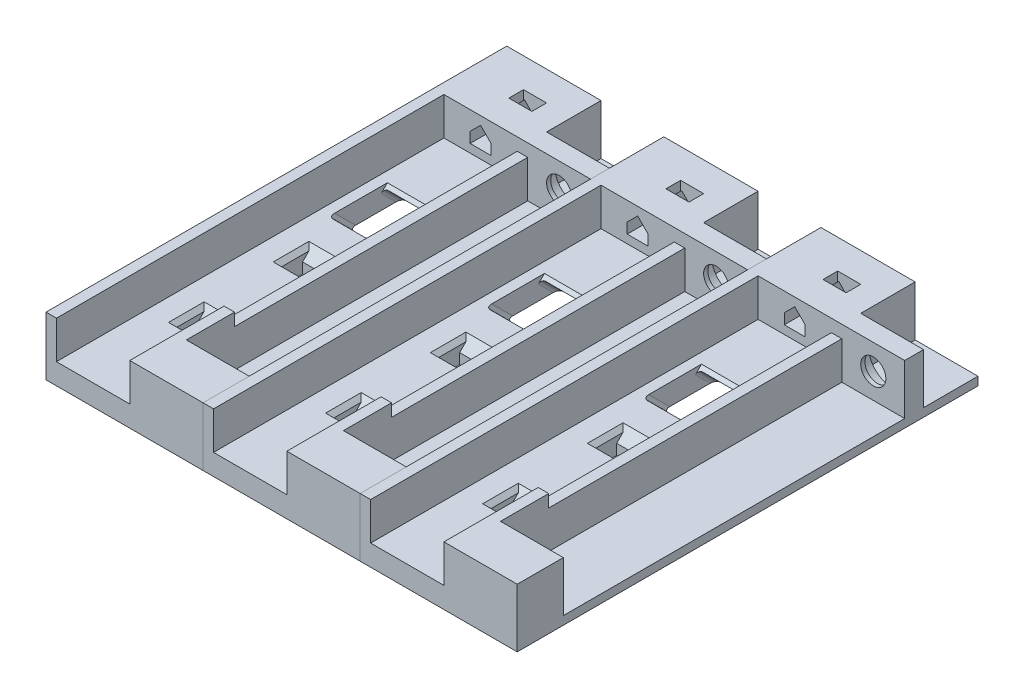
SolidWorks part; units mm, degrees
ref_plane "Płaszczyzna przednia" through (0, 0, 0) normal (0, 0, 1) x (1, 0, 0)
ref_plane "Płaszczyzna górna" through (0, 0, 0) normal (0, 1, 0) x (1, 0, 0)
ref_plane "Płaszczyzna prawa" through (0, 0, 0) normal (1, 0, 0) x (0, 0, -1)
sketch "Szkic1" plane through (0, 0, 0) normal (0, 0, 1) x (1, 0, 0)
  line L0 (0, 0) -> (0, 40.355) construction
  line L2 (17.5, 18) -> (-17.5, 18)
  line L3 (17.5, 18) -> (17.5, 0)
  line L4 (17.5, 0) -> (-17.5, 0)
  line L5 (-17.5, 18) -> (-17.5, 0)
  line L6 (17.5, 18) -> (-17.5, 0) construction
  line L7 (17.5, 0) -> (-17.5, 18) construction
  line L8 (17.5, 18) -> (22.5, 18)
  line L9 (52.5, -6) -> (22.5, -6)
  line L10 (52.5, -6) -> (52.5, 18)
  line L11 (52.5, 18) -> (22.5, 18)
  line L12 (22.5, -6) -> (22.5, 18)
  line L13 (52.5, -6) -> (22.5, 18) construction
  line L14 (52.5, 18) -> (22.5, -6) construction
  line L15 (-17.5, 18) -> (-22.5, 18)
  line L16 (-22.5, 18) -> (-22.5, -10)
  line L17 (-22.5, -10) -> (52.5, -10)
  line L18 (52.5, -10) -> (52.5, -6)
  point P3 (0, 9)
  dimension "D1" = 35
  dimension "D2" = 18
  dimension "D3" = 5
  dimension "D4" = 30
  dimension "D5" = 4
  dimension "D6" = 5
  dimension "D7" = 10
extrude "Dodanie-wyciągnięcie1" add sketch "Szkic1" against normal blind 220 contours L17 L18 L9 L12 L8 L3 L4 L5 L15 L16 region at (6, -2.12, 0)
sketch "Szkic4" plane through (0, 0, 0) normal (0, 0, 1) x (1, 0, 0)
  line L0 (52.5, -10) -> (52.5, -6) construction
  line L1 (22.5, -6) -> (52.5, -6)
  line L2 (22.5, -6) -> (22.5, 18)
  line L3 (22.5, 18) -> (52.5, 18)
  line L4 (52.5, -6) -> (52.5, 18)
  line L5 (17.5, 18) -> (22.5, 18) construction
extrude "Dodanie-wyciągnięcie3" add sketch "Szkic4" against normal blind 5
sketch "Szkic5" plane through (0, 0, 0) normal (0, 1, 0) x (1, 0, 0)
  line L0 (0, 0) -> (0, 220) construction
  line L1 (17.5, 220) -> (-17.5, 220) construction
  line L2 (17.5, 0) -> (-17.5, 0) construction
  line L3 (5, 45) -> (-5, 45)
  line L4 (5, 45) -> (5, 55)
  line L5 (5, 55) -> (-5, 55)
  line L6 (-5, 45) -> (-5, 55)
  line L7 (5, 45) -> (-5, 55) construction
  line L8 (5, 55) -> (-5, 45) construction
  line L10 (5, 105) -> (-5, 105)
  line L11 (5, 105) -> (5, 95)
  line L12 (5, 95) -> (-5, 95)
  line L13 (-5, 105) -> (-5, 95)
  line L14 (5, 105) -> (-5, 95) construction
  line L15 (5, 95) -> (-5, 105) construction
  line L16 (12.5, 150) -> (-12.5, 150)
  line L17 (12.5, 150) -> (12.5, 125)
  line L18 (12.5, 125) -> (-12.5, 125)
  line L19 (-12.5, 150) -> (-12.5, 125)
  line L20 (12.5, 150) -> (-12.5, 125) construction
  line L21 (12.5, 125) -> (-12.5, 150) construction
  point P5 (0, 50)
  point P10 (0, 137.5)
  point P13 (0, 100)
  dimension "D1" = 10
  dimension "D2" = 45
  dimension "D3" = 50
  dimension "D4" = 20
  dimension "D5" = 25
extrude "Wytnij-wyciągnięcie1" cut sketch "Szkic5" against normal blind 25 contours L6 L3 L4 L5 | L10 L13 L12 L11 region at (0, 0, -50) region at (0, 0, -100)
sketch "Szkic17" plane through (0, 0, 0) normal (0, 1, 0) x (1, 0, 0)
  line L12 (12.5, 150) -> (-12.5, 150)
  line L13 (-12.5, 150) -> (-12.5, 125)
  line L14 (-12.5, 125) -> (12.5, 125)
  line L15 (12.5, 125) -> (12.5, 150)
  line L16 (12.5, 150) -> (-12.5, 150)
  line L17 (-12.5, 150) -> (-12.5, 125)
  line L18 (-12.5, 125) -> (12.5, 125)
  line L19 (12.5, 125) -> (12.5, 150)
  dimension "D2" = 0
sketch "Szkic18" plane through (-17.5, 0, 0) normal (1, 0, 0) x (0, 0, -1)
  line L0 (150, 0) -> (169.4563, -19.4563)
  line L1 (125, 0) -> (150, 0) construction
  line L2 (220, -10) -> (0, -10) construction
  dimension "D1" = 45
sweep "Wycięcie-wyciągnięcie po ścieżce1" cut profiles "Szkic17" path "Szkic18"
sketch "Szkic6" plane through (0, 18, 0) normal (0, 1, 0) x (1, 0, 0)
  line L0 (22.5, 220) -> (22.5, 5) construction
  line L1 (17.5, 220) -> (22.5, 220)
  line L2 (17.5, 220) -> (17.5, 45)
  line L3 (17.5, 45) -> (22.5, 45)
  line L4 (22.5, 220) -> (22.5, 45)
  line L5 (17.5, 0) -> (52.5, 0) construction
  dimension "D1" = 45
extrude "Wytnij-wyciągnięcie2" cut sketch "Szkic6" against normal blind 6
sketch "Szkic7" plane through (0, 0, -5) normal (0, 0, -1) x (-1, 0, 0)
  line L0 (-37.5, 18) -> (-37.5, -6) construction
  line L1 (-52.5, 18) -> (-22.5, 18) construction
  line L2 (-52.5, -6) -> (-22.5, -6) construction
  line L3 (-43.2983, 11.7983) -> (-37.5, 17.5966)
  line L4 (-37.5, 17.5966) -> (-31.7017, 11.7983)
  line L5 (-39.5966, 15.5) -> (-35.4034, 15.5)
  line L6 (-37.5, 15.5) -> (-37.5, 14.2) construction
  line L8 (-52.5, 18) -> (-22.5, 18)
  line L9 (-52.5, 18) -> (-52.5, -6)
  line L10 (-52.5, -6) -> (-22.5, -6)
  line L11 (-22.5, 18) -> (-22.5, -6)
  circle A0 centre (-37.5, 6) radius 8.2
  line M7 (-22.5, -6) -> (-22.5, 18)
  line M8 (-22.5, 18) -> (-52.5, 18)
  line M9 (-52.5, 18) -> (-52.5, -6)
  line M10 (-52.5, -6) -> (-22.5, -6)
  dimension "D1" = 16.4
  dimension "D2" = 90
  dimension "D3" = 2.5
extrude "Dodanie-wyciągnięcie4" add sketch "Szkic7" along normal blind 10 contours A0 L3 L4 M10 M7 M8 M9 | L3 L5 L4 region at (37.5, 16.1989, -5) region at (37.5, 17.6158, -5)
sketch "Szkic9" plane through (0, 0, -15) normal (0, 0, -1) x (-1, 0, 0)
  line L1 (-52.5, 18) -> (-22.5, 18)
  line L2 (-52.5, 18) -> (-52.5, -6)
  line L3 (-52.5, -6) -> (-22.5, -6)
  line L4 (-22.5, 18) -> (-22.5, -6)
  circle A0 centre (-37.5, 6) radius 11.25
  dimension "D1" = 22.5
extrude "Dodanie-wyciągnięcie5" add sketch "Szkic9" along normal blind 7
sketch "Szkic11" plane through (0, 18, 0) normal (0, 1, 0) x (1, 0, 0)
  line L0 (-17.5, 220) -> (-17.5, 0) construction
  line L1 (-17.5, 185) -> (52.5, 185)
  line L2 (-17.5, 185) -> (-17.5, 194)
  line L3 (-17.5, 194) -> (52.5, 194)
  line L4 (52.5, 185) -> (52.5, 194)
  line L5 (52.5, 220) -> (52.5, 22) construction
  line L6 (17.5, 0) -> (-17.5, 0) construction
  line L11 (22.5, 45) -> (22.5, 220) construction
  line L12 (-17.5, 220) -> (22.5, 220)
  line L13 (-17.5, 220) -> (-17.5, 194)
  line L14 (-17.5, 194) -> (22.5, 194)
  line L15 (22.5, 220) -> (22.5, 194)
  line M8 (-17.5, 0) -> (-17.5, 220)
  dimension "D1" = 185
  dimension "D2" = 9
extrude "Dodanie-wyciągnięcie6" add sketch "Szkic11" against normal up to surface (24 mm away) contours L15 L12 L3 M8 | L1 L4 L3 M8 region at (17.5, 18, -189.5) region at (2.5, 18, -207) up to face at (37.5, -6, -121)
sketch "Szkic12" plane through (0, 0, -194) normal (0, 0, -1) x (-1, 0, 0)
  circle A0 centre (-37.5, 6) radius 11.25 construction
  circle A1 centre (-37.5, 6) radius 11.25
extrude "Wytnij-wyciągnięcie3" cut sketch "Szkic12" against normal blind 7
sketch "Szkic13" plane through (0, 0, -187) normal (0, 0, -1) x (-1, 0, 0)
  circle A0 centre (-37.5, 6) radius 6
  dimension "D1" = 12
extrude "Wytnij-wyciągnięcie4" cut sketch "Szkic13" against normal blind 7
sketch "Szkic14" plane through (0, 0, -185) normal (0, 0, 1) x (1, 0, 0)
  line L0 (0, 0) -> (0, 18) construction
  line L1 (-17.5, 18) -> (52.5, 18) construction
  line L2 (-5, 9) -> (0, 14)
  line L7 (-5, 9) -> (5, 9)
  line L8 (-5, 9) -> (-5, 4)
  line L9 (-5, 4) -> (5, 4)
  line L10 (5, 9) -> (5, 4)
  line L11 (-5, 9) -> (5, 4) construction
  line L12 (-5, 4) -> (5, 9) construction
  line L13 (0, 14) -> (5, 9)
  point P5 (-0.2622, 7.2089)
  point P13 (0, 6.5)
  dimension "D1" = 5
  dimension "D2" = 10
  dimension "D3" = 45
  dimension "D4" = 4
extrude "Wytnij-wyciągnięcie5" cut sketch "Szkic14" against normal blind 200 contours L10 L7 L8 L9 | L13 L2 L7 region at (0, 10.6667, -185) region at (0, 6.5, -185)
sketch "Szkic15" plane through (0, 4, 0) normal (0, 1, 0) x (1, 0, 0)
  line L0 (-5, 202.5) -> (11.7711, 202.5) construction
  line L2 (10.5, 206) -> (-0.5, 206)
  line L3 (10.5, 206) -> (10.5, 199)
  line L4 (-5, 220) -> (-5, 185)
  line L5 (-5, 185) -> (5, 185)
  line L6 (5, 185) -> (5, 220)
  line L7 (5, 220) -> (-5, 220)
  line L8 (-5, 220) -> (-5, 185)
  line L9 (-5, 185) -> (5, 185)
  line L10 (5, 185) -> (5, 220)
  line L11 (5, 220) -> (-5, 220)
  line L12 (10.5, 199) -> (-0.5, 199)
  line L13 (-0.5, 206) -> (-0.5, 199)
  line L14 (10.5, 206) -> (-0.5, 199) construction
  line L15 (10.5, 199) -> (-0.5, 206) construction
  point P6 (5, 202.5)
  point P11 (5, 202.5)
  dimension "D2" = 11
  dimension "D3" = 7
  dimension "D1" = 0
extrude "Wytnij-wyciągnięcie6" cut sketch "Szkic15" along normal mid plane 200 contours L12 L3 L2 L10 | L2 L13 L12 L10 region at (7.75, 4, -202.5) region at (2.25, 4, -202.5)
chamfer "Sfazowanie1" distance 5 angle 45 2 edges at (0, 0, -105) (0, 0, -55)
chamfer "Sfazowanie3" distance 2 angle 45 6 edges at (5, 0, -102.5) (0, 0, -95) (-5, 0, -102.5) (5, 0, -52.5) (0, 0, -45) (-5, 0, -52.5)
chamfer "Sfazowanie5" distance 3 angle 45 1 edges at (0, 0, -150) first distance on face at (0, 0, -92.5)
fillet "Zaokrąglenie3" radius 2 4 edges at (12.5, -5, -130) (12.5, -5.75, -155.75) (-12.5, -5, -130) (-12.5, -5.75, -155.75)
pattern_linear "Szyk liniowy1" count 3 spacing 75 along (1, 0, 0) of bodies 112
